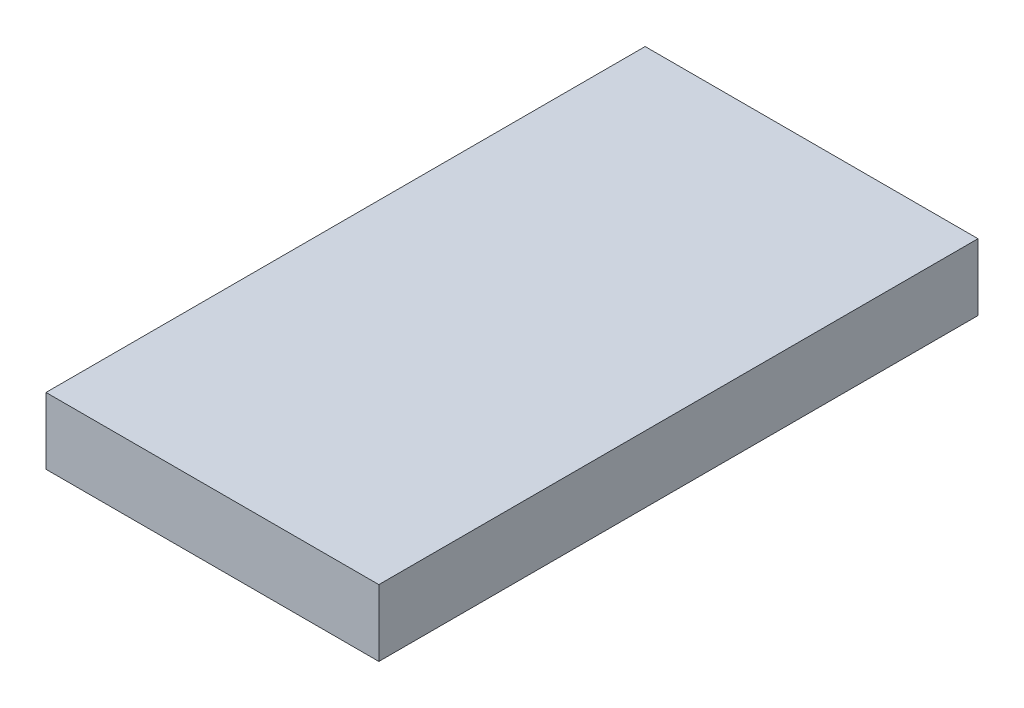
SolidWorks part; units mm, degrees
ref_plane "Front Plane" through (0, 0, 0) normal (0, 0, 1) x (1, 0, 0)
ref_plane "Top Plane" through (0, 0, 0) normal (0, 1, 0) x (1, 0, 0)
ref_plane "Right Plane" through (0, 0, 0) normal (1, 0, 0) x (0, 0, -1)
sketch "Sketch1" plane through (0, 0, 0) normal (0, 1, 0) x (1, 0, 0)
  line L1 (-125, -25) -> (125, -25)
  line L2 (-125, -25) -> (-125, 25)
  line L3 (-125, 25) -> (125, 25)
  line L4 (125, -25) -> (125, 25)
  line L5 (-125, -25) -> (125, 25) construction
  line L6 (-125, 25) -> (125, -25) construction
  point P0 (0, 0)
  dimension "D1" = 250
  dimension "D2" = 50
extrude "Boss-Extrude1" add sketch "Sketch1" along normal blind 10
fillet "Fillet2" radius 25 2 edges at (-125, 5, 25) (-125, 5, -25)
sketch "Sketch4" plane through (0, 10, 0) normal (0, 1, 0) x (1, 0, 0)
  circle A0 centre (-100, 0) radius 6.75
  dimension "D1" = 13.5
extrude "Cut-Extrude3" cut sketch "Sketch4" against normal through all
sketch "Sketch5" plane through (0, 0, -25) normal (0, 0, -1) x (-1, 0, 0)
  line L0 (-125, 10) -> (100, 10) construction
  line L1 (-125, 0) -> (-15, 0)
  line L2 (-125, 0) -> (-125, 10)
  line L3 (-125, 10) -> (-15, 10)
  line L4 (-15, 0) -> (-15, 10)
  dimension "D1" = 110
extrude "Boss-Extrude2" add sketch "Sketch5" along normal blind 20
sketch "Sketch6" plane through (0, 0, 25) normal (0, 0, 1) x (1, 0, 0)
  line L0 (-100, 10) -> (125, 10) construction
  line L1 (125, 0) -> (75, 0)
  line L2 (125, 0) -> (125, 10)
  line L3 (125, 10) -> (75, 10)
  line L4 (75, 0) -> (75, 10)
  dimension "D1" = 50
extrude "Boss-Extrude3" add sketch "Sketch6" along normal blind 20
sketch "Sketch7" plane through (0, 0, 0) normal (0, -1, 0) x (1, 0, 0)
  circle A0 centre (70, -25) radius 2.5527 construction
  circle A1 centre (70, -25) radius 2.5527
extrude "Cut-Extrude4" cut sketch "Sketch7" against normal through all
sketch "Sketch8" plane through (0, 0, 0) normal (0, -1, 0) x (1, 0, 0)
  line L1 (75, 25) -> (-133.8592, 25)
  line L2 (75, 25) -> (75, -54.6073)
  line L3 (75, -54.6073) -> (-133.8592, -54.6073)
  line L4 (-133.8592, 25) -> (-133.8592, -54.6073)
extrude "Cut-Extrude5" cut sketch "Sketch8" against normal through all
